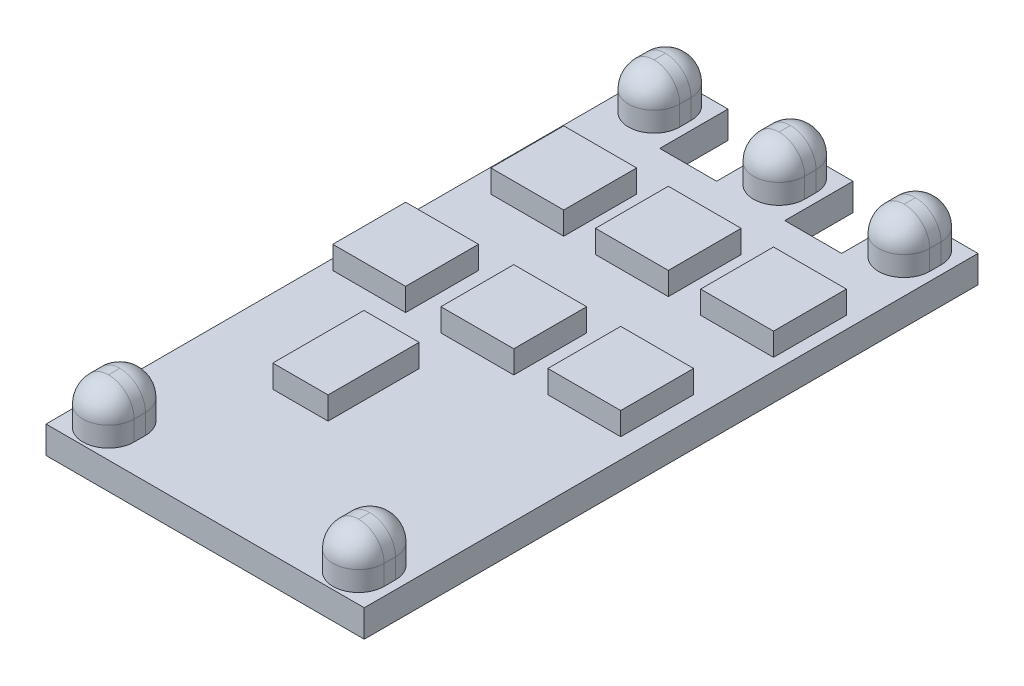
SolidWorks part; units mm, degrees
ref_plane "Front Plane" through (0, 0, 0) normal (0, 0, 1) x (1, 0, 0)
ref_plane "Top Plane" through (0, 0, 0) normal (0, 1, 0) x (1, 0, 0)
ref_plane "Right Plane" through (0, 0, 0) normal (1, 0, 0) x (0, 0, -1)
sketch "Sketch1" plane through (0, 0, 0) normal (0, 1, 0) x (1, 0, 0)
  line L0 (0, 21.6721) -> (0, -24.4888) construction
  line L1 (-7, 12) -> (7, 12)
  line L2 (-7, 12) -> (-7, -12)
  line L3 (-7, -12) -> (7, -12)
  line L4 (7, 12) -> (7, -12)
  line L5 (-7, 12) -> (7, -12) construction
  line L6 (-7, -12) -> (7, 12) construction
  line L8 (-1.5, 15) -> (1.5, 15)
  line L9 (-1.5, 15) -> (-1.5, 12)
  line L10 (-1.5, 12) -> (1.5, 12)
  line L11 (1.5, 15) -> (1.5, 12)
  line L12 (-1.5, 15) -> (1.5, 12) construction
  line L13 (-1.5, 12) -> (1.5, 15) construction
  line L14 (-7, 12) -> (-4, 12)
  line L15 (-7, 12) -> (-7, 15)
  line L16 (-7, 15) -> (-4, 15)
  line L17 (-4, 12) -> (-4, 15)
  line L18 (7, 12) -> (4, 12)
  line L19 (7, 12) -> (7, 15)
  line L20 (7, 15) -> (4, 15)
  line L21 (4, 12) -> (4, 15)
  point P0 (0, 0)
  point P7 (0, 13.5)
  dimension "D1" = 24
  dimension "D2" = 14
  dimension "D3" = 3
  dimension "D4" = 3
extrude "PCB" add sketch "Sketch1" along normal blind 1.2 contours L4 L1 L2 L3 | L1 L17 L16 L15 | L11 L8 L9 L1 | L21 L1 L19 L20 region at (-5.5, 0, -13.5) region at (0, 0, 0) region at (0, 0, -13.5) region at (5.5, 0, -13.5)
sketch "Sketch5" plane through (0, 1.2, 0) normal (0, 1, 0) x (1, 0, 0)
  line L0 (-7, 12) -> (7, 12) construction
  line L1 (-7, 15) -> (-7, -12) construction
  line L2 (7, 15) -> (7, -12) construction
  line L3 (-4, 12) -> (-1.5, 12) construction
  line L4 (-5.5, 15) -> (-5.5, 12) construction
  line L5 (-7, 15) -> (-4, 15) construction
  line L6 (-7, 13.5) -> (7, 13.5) construction
  line L7 (0, 15) -> (0, 12) construction
  line L8 (-1.5, 15) -> (1.5, 15) construction
  line L9 (5.5, 15) -> (5.5, 12) construction
  line L10 (7, 15) -> (4, 15) construction
  line L11 (-5.5, 13.25) -> (-5.5, 13.75) construction
  line L12 (-6.625, 13.25) -> (-6.625, 13.75)
  line L13 (-4.375, 13.25) -> (-4.375, 13.75)
  line L14 (0, 13.75) -> (0, 13.25) construction
  line L15 (1.125, 13.75) -> (1.125, 13.25)
  line L16 (-1.125, 13.75) -> (-1.125, 13.25)
  line L17 (5.5, 13.75) -> (5.5, 13.25) construction
  line L18 (6.625, 13.75) -> (6.625, 13.25)
  line L19 (4.375, 13.75) -> (4.375, 13.25)
  line L20 (-4, 12) -> (-4, 15) construction
  line L21 (-7, -12) -> (7, -12)
  line L22 (-7, -12) -> (-7, -9)
  line L23 (-7, -9) -> (7, -9)
  line L24 (7, -12) -> (7, -9)
  line L25 (-7, -9) -> (-4, -9)
  line L26 (-7, -9) -> (-7, -12)
  line L27 (-7, -12) -> (-4, -12)
  line L28 (-4, -9) -> (-4, -12)
  line L29 (-5.5, -9) -> (-5.5, -12) construction
  line L30 (-5.5, -10.25) -> (-5.5, -10.75) construction
  line L31 (-4.375, -10.25) -> (-4.375, -10.75)
  line L32 (-6.625, -10.25) -> (-6.625, -10.75)
  line L33 (0, -9) -> (0, -12) construction
  line L34 (5.5, -10.25) -> (5.5, -10.75) construction
  line L35 (4.375, -10.25) -> (4.375, -10.75)
  line L36 (6.625, -10.25) -> (6.625, -10.75)
  arc A0 (-6.625, 13.25) -> (-4.375, 13.25) centre (-5.5, 13.25) ccw
  arc A1 (-4.375, 13.75) -> (-6.625, 13.75) centre (-5.5, 13.75) ccw
  arc A2 (1.125, 13.75) -> (-1.125, 13.75) centre (0, 13.75) ccw
  arc A3 (-1.125, 13.25) -> (1.125, 13.25) centre (0, 13.25) ccw
  arc A4 (6.625, 13.75) -> (4.375, 13.75) centre (5.5, 13.75) ccw
  arc A5 (4.375, 13.25) -> (6.625, 13.25) centre (5.5, 13.25) ccw
  arc A6 (-4.375, -10.25) -> (-6.625, -10.25) centre (-5.5, -10.25) ccw
  arc A7 (-6.625, -10.75) -> (-4.375, -10.75) centre (-5.5, -10.75) ccw
  arc A8 (4.375, -10.25) -> (6.625, -10.25) centre (5.5, -10.25) cw
  arc A9 (6.625, -10.75) -> (4.375, -10.75) centre (5.5, -10.75) cw
  point P14 (-5.5, 13.5)
  point P25 (-5.5, 13.5)
  point P32 (0, 13.5)
  point P39 (5.5, 13.5)
  point P57 (-5.5, -10.5)
  point P66 (5.5, -10.5)
  dimension "D1" = 2.25
  dimension "D2" = 0.5
  dimension "D3" = 3
extrude "Solder joints" add sketch "Sketch5" along normal blind 2 contours L13 A1 L12 A0 | L16 A3 L15 A2 | L19 A5 L18 A4 | L32 A7 L31 A6 | A9 L36 A8 L35 region at (-5.5, 1.2, -13.5) region at (0, 1.2, -13.5) region at (5.5, 1.2, -13.5) region at (-5.5, 1.2, 10.5) region at (5.5, 1.2, 10.5)
fillet "Solder fillets" radius 1.125 20 edges at (-5.5, 3.2, 9.125) (-4.375, 3.2, 10.5) (-5.5, 3.2, 11.875) (-6.625, 3.2, 10.5) (4.375, 3.2, 10.5) (5.5, 3.2, 9.125) (6.625, 3.2, 10.5) (5.5, 3.2, 11.875) (5.5, 3.2, -14.875) (6.625, 3.2, -13.5) (5.5, 3.2, -12.125) (4.375, 3.2, -13.5) (0, 3.2, -14.875) (1.125, 3.2, -13.5) (0, 3.2, -12.125) (-1.125, 3.2, -13.5) (-5.5, 3.2, -12.125) (-6.625, 3.2, -13.5) (-5.5, 3.2, -14.875) (-4.375, 3.2, -13.5)
sketch "Sketch2" plane through (0, 1.2, 0) normal (0, 1, 0) x (1, 0, 0)
  line L1 (-5.9719, 9.747) -> (-2.7662, 9.747)
  line L2 (-5.9719, 9.747) -> (-5.9719, 6.5413)
  line L3 (-5.9719, 6.5413) -> (-2.7662, 6.5413)
  line L4 (-2.7662, 9.747) -> (-2.7662, 6.5413)
  line L5 (-1.3702, 9.747) -> (1.8355, 9.747)
  line L6 (-1.3702, 9.747) -> (-1.3702, 6.5413)
  line L7 (-1.3702, 6.5413) -> (1.8355, 6.5413)
  line L8 (1.8355, 9.747) -> (1.8355, 6.5413)
  line L9 (3.2574, 9.747) -> (6.4631, 9.747)
  line L10 (3.2574, 9.747) -> (3.2574, 6.5413)
  line L11 (3.2574, 6.5413) -> (6.4631, 6.5413)
  line L12 (6.4631, 9.747) -> (6.4631, 6.5413)
  line L13 (-3.335, 3.3614) -> (-6.5407, 3.3614)
  line L14 (-3.335, 3.3614) -> (-3.335, 0.1557)
  line L15 (-3.335, 0.1557) -> (-6.5407, 0.1557)
  line L16 (-6.5407, 3.3614) -> (-6.5407, 0.1557)
  line L17 (-1.7838, 3.3614) -> (1.4219, 3.3614)
  line L18 (-1.7838, 3.3614) -> (-1.7838, 0.1557)
  line L19 (-1.7838, 0.1557) -> (1.4219, 0.1557)
  line L20 (1.4219, 3.3614) -> (1.4219, 0.1557)
  line L21 (2.9213, 3.3614) -> (6.1271, 3.3614)
  line L22 (2.9213, 3.3614) -> (2.9213, 0.1557)
  line L23 (2.9213, 0.1557) -> (6.1271, 0.1557)
  line L24 (6.1271, 3.3614) -> (6.1271, 0.1557)
  line L25 (-3.335, -1.6799) -> (-0.9048, -1.6799)
  line L26 (-3.335, -1.6799) -> (-3.335, -5.687)
  line L27 (-3.335, -5.687) -> (-0.9048, -5.687)
  line L28 (-0.9048, -1.6799) -> (-0.9048, -5.687)
extrude "Top components" add sketch "Sketch2" along normal blind 1
sketch "Sketch3" plane through (0, 0, 0) normal (0, -1, 0) x (1, 0, 0)
  line L1 (-2.7921, 0) -> (1.2409, 0)
  line L2 (-2.7921, 0) -> (-2.7921, 4.0583)
  line L3 (-2.7921, 4.0583) -> (1.2409, 4.0583)
  line L4 (1.2409, 0) -> (1.2409, 4.0583)
  line L5 (-5.8944, -3.9818) -> (-2.7921, -3.9818)
  line L6 (-5.8944, -3.9818) -> (-5.8944, -6.9032)
  line L7 (-5.8944, -6.9032) -> (-2.7921, -6.9032)
  line L8 (-2.7921, -3.9818) -> (-2.7921, -6.9032)
  line L9 (-1.3185, -3.9818) -> (1.4995, -3.9818)
  line L10 (-1.3185, -3.9818) -> (-1.3185, -6.9032)
  line L11 (-1.3185, -6.9032) -> (1.4995, -6.9032)
  line L12 (1.4995, -3.9818) -> (1.4995, -6.9032)
  line L13 (3.0765, -3.9818) -> (5.9461, -3.9818)
  line L14 (3.0765, -3.9818) -> (3.0765, -6.9032)
  line L15 (3.0765, -6.9032) -> (5.9461, -6.9032)
  line L16 (5.9461, -3.9818) -> (5.9461, -6.9032)
  line L17 (3.516, 9.4874) -> (5.3515, 9.4874)
  line L18 (3.516, 9.4874) -> (3.516, 6.3592)
  line L19 (3.516, 6.3592) -> (5.3515, 6.3592)
  line L20 (5.3515, 9.4874) -> (5.3515, 6.3592)
extrude "Bottom components" add sketch "Sketch3" along normal blind 1
ref_plane "Motor wires plane" through (0, 0, -13.5) normal (0, 0, -1) x (-1, 0, 0)
ref_plane "Control wires plane" through (0, 0, 10.5) normal (0, 0, 1) x (1, 0, 0)
sketch "Motor wire locations" plane through (0, 0, -13.5) normal (0, 0, -1) x (-1, 0, 0)
  line L0 (7, 1.2) -> (4, 1.2) construction
  line L1 (1.5, 1.2) -> (-1.5, 1.2) construction
  line L2 (-7, 1.2) -> (-4, 1.2) construction
  line L3 (7, 1.2) -> (4, 1.2)
  line L4 (1.5, 1.2) -> (-1.5, 1.2)
  line L5 (-7, 1.2) -> (-4, 1.2)
  line L6 (-7, 2.7) -> (-4, 1.2) construction
  line L7 (-7, 1.2) -> (-4, 1.2)
  line L8 (-7, 1.2) -> (-7, 2.7)
  line L9 (-7, 2.7) -> (-4, 2.7)
  line L10 (-4, 1.2) -> (-4, 2.7)
  line L11 (-1.5, 2.7) -> (1.5, 1.2) construction
  line L12 (-1.5, 1.2) -> (1.5, 1.2)
  line L13 (-1.5, 1.2) -> (-1.5, 2.7)
  line L14 (-1.5, 2.7) -> (1.5, 2.7)
  line L15 (1.5, 1.2) -> (1.5, 2.7)
  line L16 (4, 1.2) -> (7, 1.2)
  line L17 (4, 1.2) -> (4, 2.7)
  line L18 (4, 2.7) -> (7, 2.7)
  line L19 (7, 1.2) -> (7, 2.7)
  line L20 (4, 2.7) -> (7, 1.2) construction
  point P9 (-5.5, 1.95)
  point P14 (0, 1.95)
  point P15 (5.5, 1.95)
  dimension "D1" = 1.5
sketch "Control wire locations" plane through (0, 0, 10.5) normal (0, 0, 1) x (1, 0, 0)
  line L0 (-4, 1.2) -> (-4, 2.7) construction
  line L1 (-7, 1.2) -> (-4, 1.2)
  line L2 (-7, 1.2) -> (-7, 2.7)
  line L3 (-7, 2.7) -> (-4, 2.7)
  line L4 (-4, 1.2) -> (-4, 2.7)
  line L5 (-4, 2.7) -> (-7, 2.7) construction
  line L6 (-7, 1.2) -> (-4, 2.7) construction
  line L7 (0, 4.0612) -> (0, -2.6256) construction
  line L8 (-7, 1.2) -> (-7, 2.7) construction
  line L9 (-7, 1.2) -> (-4, 1.2) construction
  line L10 (7, 1.2) -> (4, 2.7) construction
  line L11 (4, 1.2) -> (4, 2.7)
  line L12 (7, 1.2) -> (4, 1.2)
  line L13 (7, 1.2) -> (7, 2.7)
  line L14 (7, 2.7) -> (4, 2.7)
  point P4 (5.5, 1.95)
  point P9 (-5.5, 1.95)
other "A" parameters "Diameter"=1.5, "StubLength"=3
ref_axis "Axis1" through (5.5, 1.95, -23.5) along (0, 0, 1)
other "B" parameters "Diameter"=1.5, "StubLength"=3
ref_axis "Axis2" through (0, 1.95, -23.5) along (0, 0, 1)
other "C" parameters "Diameter"=1.5, "StubLength"=3
ref_axis "Axis3" through (-5.5, 1.95, -23.5) along (0, 0, 1)
other "NEG" parameters "Diameter"=1.5, "StubLength"=3
ref_axis "Axis4" through (-5.5, 1.95, 20.5) along (0, 0, -1)
other "POS" parameters "Diameter"=1.5, "StubLength"=3
ref_axis "Axis5" through (5.5, 1.95, 20.5) along (0, 0, -1)
